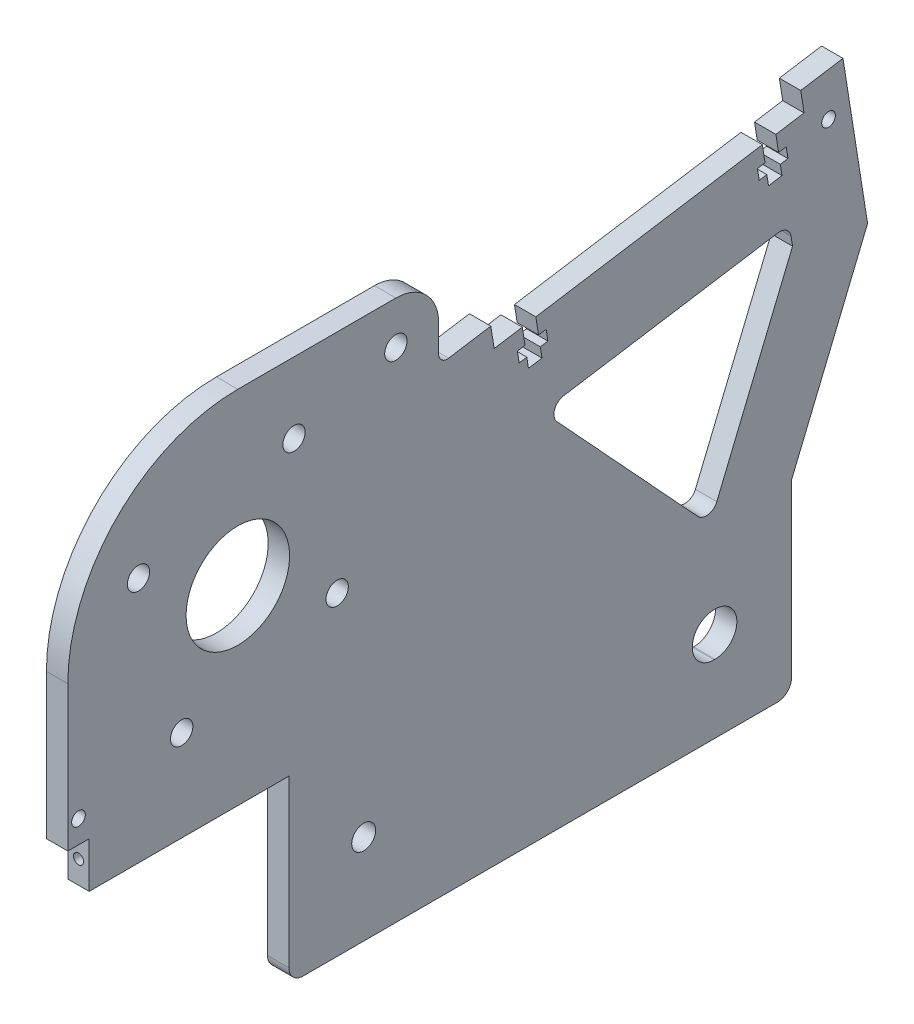
SolidWorks part; units mm, degrees
ref_plane "Front Plane" through (0, 0, 0) normal (0, 0, 1) x (1, 0, 0)
ref_plane "Top Plane" through (0, 0, 0) normal (0, 1, 0) x (1, 0, 0)
ref_plane "Right Plane" through (0, 0, 0) normal (1, 0, 0) x (0, 0, -1)
sketch "Sketch1" plane through (0, 0, 0) normal (1, 0, 0) x (0, 0, -1)
  line L0 (-28.1703, 0) -> (77.3828, 0)
  line L1 (80.5578, 3.175) -> (80.5578, 41.307)
  line L2 (-80.5578, 82.55) -> (-80.5578, 50.292)
  line L3 (4.1952, 102.9251) -> (13.6029, 104.4151)
  line L4 (-75.7953, 50.292) -> (-75.7953, 40.132)
  line L5 (-80.5578, 50.292) -> (-75.7953, 50.292)
  line L6 (63.5398, 20.066) -> (63.2858, 20.066) construction
  line L7 (-75.7953, 40.132) -> (-31.3453, 40.132)
  line L8 (1.9922, 110.875) -> (1.9922, 104.8066)
  line L9 (-42.7078, 120.4) -> (-7.5328, 120.4)
  line L10 (-31.3453, 40.132) -> (-31.3453, 3.175)
  line L11 (-37.7254, 96.5488) -> (76.315, 55.9603) construction
  line L12 (-52.5202, 71.3918) -> (38.3797, -8.5448) construction
  line L13 (63.5398, 15.2273) -> (63.2858, 15.2273)
  line L14 (63.5398, 24.9047) -> (63.2858, 24.9047)
  line L15 (4.1952, 102.9251) -> (101.0919, 102.9251) construction
  line L16 (13.6029, 104.4151) -> (14.348, 99.7113)
  line L17 (14.348, 99.7113) -> (20.6198, 100.7046)
  line L18 (83.338, 110.6382) -> (82.593, 115.3421)
  line L19 (82.593, 115.3421) -> (92.0007, 116.8321)
  line L20 (92.0007, 116.8321) -> (97.4765, 82.2596)
  line L21 (97.4765, 82.2596) -> (80.5578, 41.307)
  line L22 (20.6198, 100.7046) -> (21.2208, 96.9102)
  line L23 (21.2208, 96.9102) -> (19.5274, 96.642)
  line L24 (19.5274, 96.642) -> (19.9198, 94.1646)
  line L25 (19.9198, 94.1646) -> (21.6131, 94.4328)
  line L26 (26.317, 95.1778) -> (25.9246, 97.6552)
  line L27 (25.9246, 97.6552) -> (24.2312, 97.387)
  line L28 (24.2312, 97.387) -> (23.6303, 101.1814)
  line L29 (23.6303, 101.1814) -> (74.0557, 109.168)
  line L30 (77.0662, 109.6449) -> (83.338, 110.6382)
  line L31 (80.4436, 88.3207) -> (80.7745, 86.2313)
  line L38 (21.6131, 94.4328) -> (21.9857, 92.0809)
  line L39 (21.9857, 92.0809) -> (24.9961, 92.5577)
  line L40 (24.9961, 92.5577) -> (24.6236, 94.9096)
  line L41 (24.6236, 94.9096) -> (26.317, 95.1778)
  line L46 (74.0557, 109.168) -> (74.6567, 105.3736)
  line L47 (77.5375, 90.432) -> (29.7985, 82.8709)
  line L48 (28.3297, 78.6391) -> (59.6993, 44.664)
  line L49 (63.9131, 45.4172) -> (80.7745, 86.2313)
  line L50 (74.6567, 105.3736) -> (72.9633, 105.1054)
  line L51 (72.9633, 105.1054) -> (73.3557, 102.628)
  line L52 (73.3557, 102.628) -> (75.0491, 102.8962)
  line L53 (79.7529, 103.6412) -> (79.3605, 106.1186)
  line L54 (79.3605, 106.1186) -> (77.6672, 105.8504)
  line L55 (77.6672, 105.8504) -> (77.0662, 109.6449)
  line L56 (75.0491, 102.8962) -> (75.4216, 100.5443)
  line L57 (75.4216, 100.5443) -> (78.432, 101.0211)
  line L58 (78.432, 101.0211) -> (78.0595, 103.373)
  line L59 (78.0595, 103.373) -> (79.7529, 103.6412)
  arc A0 (63.5398, 15.2273) -> (63.5398, 24.9047) centre (63.5398, 20.066) ccw
  circle A1 centre (-42.7078, 82.55) radius 31.5 construction
  circle A2 centre (63.5398, 20.066) radius 78.105 construction
  circle A3 centre (63.5398, 20.066) radius 38.1 construction
  circle A4 centre (-42.7078, 82.55) radius 14.859 construction
  arc A5 (-42.7078, 120.4) -> (-80.5578, 82.55) centre (-42.7078, 82.55) ccw
  arc A6 (-28.1703, 0) -> (-31.3453, 3.175) centre (-28.1703, 3.175) cw
  arc A7 (77.3828, 0) -> (80.5578, 3.175) centre (77.3828, 3.175) ccw
  circle A9 centre (-7.5328, 110.875) radius 6.35 construction
  circle A10 centre (-55.209, 60.4394) radius 2.4892
  circle A11 centre (-14.6922, 20.066) radius 2.667
  circle A12 centre (-20.5972, 70.0488) radius 2.4892
  circle A13 centre (-64.8184, 95.0512) radius 2.4892
  circle A14 centre (-30.2065, 104.6606) radius 2.4892
  circle A15 centre (-78.1765, 55.372) radius 1.524
  circle A16 centre (-42.7078, 82.55) radius 11.5228
  arc A17 (63.2858, 24.9047) -> (63.2858, 15.2273) centre (63.2858, 20.066) ccw
  arc A18 (-7.5328, 120.4) -> (1.9922, 110.875) centre (-7.5328, 110.875) cw
  circle A19 centre (-7.5328, 110.875) radius 2.4892
  arc A20 (4.1952, 102.9251) -> (1.9922, 104.8066) centre (3.8972, 104.8066) cw
  circle A22 centre (88.7869, 106.6794) radius 1.524
  arc A24 (59.6993, 44.664) -> (63.9131, 45.4172) centre (61.5655, 46.387) ccw
  arc A25 (29.7985, 82.8709) -> (28.3297, 78.6391) centre (30.1958, 80.3622) ccw
  arc A26 (77.5375, 90.432) -> (80.4436, 88.3207) centre (77.9349, 87.9233) cw
  point P39 (63.4128, 20.066)
  dimension "D4" = 9.6774
  dimension "D7" = 29.718
  dimension "D8" = 63
  dimension "D9" = 6.35
  dimension "D12" = 3.175
  dimension "D13" = 4.7625
  dimension "D14" = 76.2
  dimension "D15" = 156.21
  dimension "D18" = 5.334
  dimension "D19" = 9.525
  dimension "D20" = 9.525
  dimension "D23" = 3.048
  dimension "D27" = 73.025
  dimension "D28" = 12.7
  dimension "D29" = 4.9784
  dimension "D31" = 1.905
  dimension "D33" = 3.048
  dimension "D42" = 2.54
  dimension "D44" = 86.36
  dimension "D48" = 3.048
  dimension "D49" = 9.525
  dimension "D2" = 40.132
  dimension "D3" = 20.066
  dimension "D5" = 17.018
  dimension "D6" = 44.45
  dimension "D10" = 161.1156
  dimension "D11" = 95.25
  dimension "D17" = 9
  dimension "D21" = 4.7625
  dimension "D22" = 10.16
  dimension "D24" = 5.08
  dimension "D25" = 2.3813
  dimension "D26" = 0.254
  dimension "D16" = 88.9
  dimension "D30" = 9.525
  dimension "D34" = 19.05
  dimension "D35" = 8.7312
  dimension "D36" = 2.5083
  dimension "D37" = 6.477
  dimension "D38" = 6.35
  dimension "D40" = 15.875
  dimension "D45" = 6.35
  dimension "D46" = 6.35
  dimension "D47" = 4.7625
  dimension "D50" = 5.08
  dimension "D39" = 2
extrude "Boss-Extrude1" add sketch "Sketch1" along normal blind 4.7625
sketch "Sketch2" plane through (0, 0, 75.7953) normal (0, 0, 1) x (1, 0, 0)
  line L0 (4.7625, 50.292) -> (4.7625, 40.132) construction
  line L1 (4.7625, 40.132) -> (0, 40.132) construction
  circle A0 centre (2.3813, 45.212) radius 1.1303
  point P4 (4.7625, 45.212)
  point P7 (2.3813, 40.132)
  dimension "D1" = 2.2606
extrude "Cut-Extrude1" cut sketch "Sketch2" against normal blind 6.35
